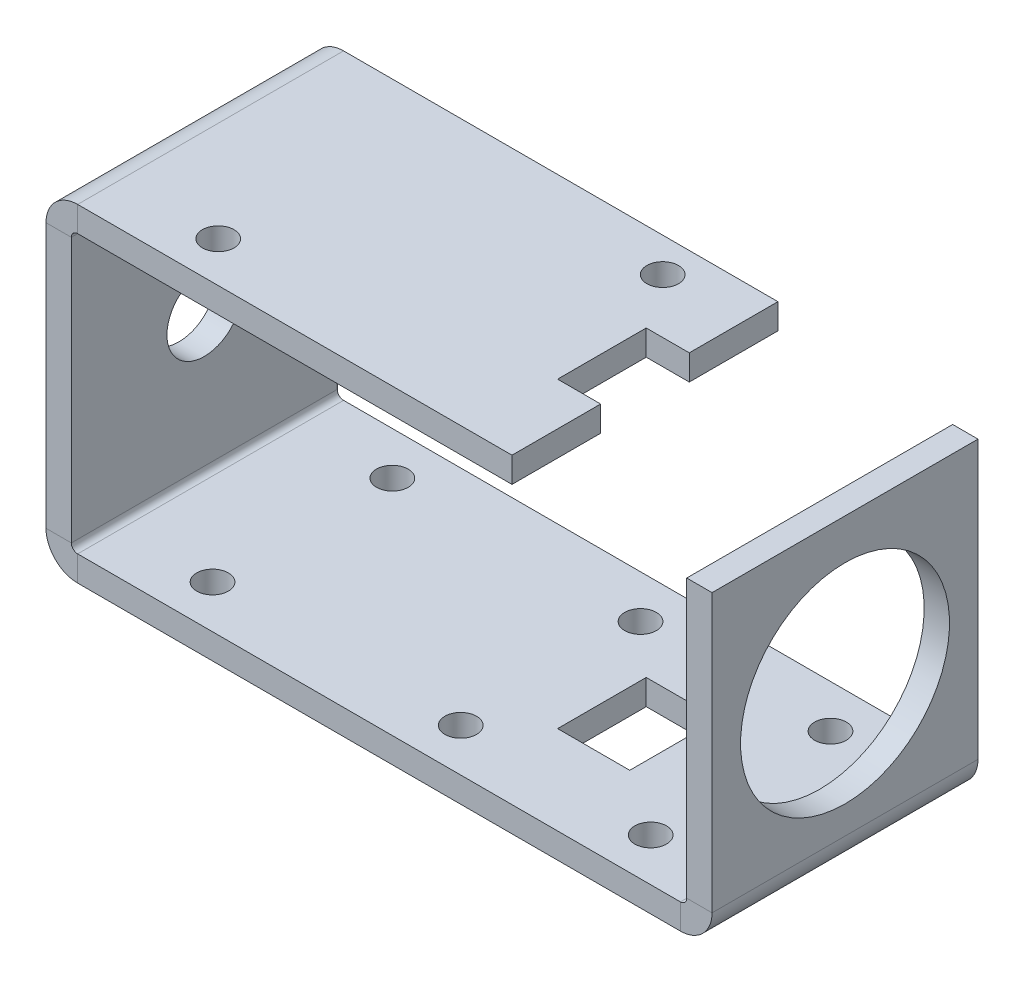
SolidWorks part; units mm, degrees
note: The reader was unsure of these and kept them because the rebuilt part matched: flange length of "Edge-Flange1", "Edge-Flange2", "Edge-Flange3".
ref_plane "Front Plane" through (0, 0, 0) normal (0, 0, 1) x (1, 0, 0)
ref_plane "Top Plane" through (0, 0, 0) normal (0, 1, 0) x (1, 0, 0)
ref_plane "Right Plane" through (0, 0, 0) normal (1, 0, 0) x (0, 0, -1)
sketch "Sketch1" plane through (0, 0, 0) normal (0, 1, 0) x (1, 0, 0)
  line L1 (-26.3, -10.5) -> (26.3, -10.5)
  line L2 (-26.3, -10.5) -> (-26.3, 10.5)
  line L3 (-26.3, 10.5) -> (26.3, 10.5)
  line L4 (26.3, -10.5) -> (26.3, 10.5)
  line L5 (-26.3, -10.5) -> (26.3, 10.5) construction
  line L6 (-26.3, 10.5) -> (26.3, -10.5) construction
  point P0 (0, 0)
  dimension "D1" = 21
  dimension "D2" = 52.6
base flange "Base-Flange1" sketch "Sketch1" thickness 2 reverse thickness direction no parameters "D1"=1
edge flange "Edge-Flange1" sketch "Sketch8" flange angle 90 flange length 25.9 flange position material inside bend radius 0.5 thickness 2 relief rectangular parameters "D6"=10
sketch "Sketch8" plane through (-26.3, 0, 0) normal (-1, 0, 0) x (0, 0, 1)
  line L0 (-10.5, 0) -> (10.5, 0) construction
  line L1 (-10.5, 0) -> (10.5, 0)
  line L2 (-10.5, 0) -> (-10.5, 23.9)
  line L3 (-10.5, 23.9) -> (10.5, 23.9)
  line L4 (10.5, 23.9) -> (10.5, 0)
bend "EdgeBend1" bend radius 0.5 bend angle 90 parameters "D5"=1
edge flange "Edge-Flange2" sketch "Sketch11" flange angle 90 flange length 36.8 flange position material inside bend radius 0.5 thickness 2 relief rectangular parameters "D6"=10
sketch "Sketch11" plane through (-24.3, 23.9, 0) normal (0, 1, 0) x (0, 0, 1)
  line L0 (10.5, 0) -> (-10.5, 0) construction
  line L1 (10.5, 0) -> (-10.5, 0)
  line L2 (-10.5, 0) -> (-10.5, 34.8)
  line L3 (-10.5, 34.8) -> (10.5, 34.8)
  line L4 (10.5, 34.8) -> (10.5, 0)
bend "EdgeBend2" bend radius 0.5 bend angle 90 parameters "D5"=2
edge flange "Edge-Flange3" sketch "Sketch14" flange angle 90 flange length 23.6 flange position material inside bend radius 0.5 thickness 2 relief rectangular parameters "D6"=10
sketch "Sketch14" plane through (26.3, 0, 0) normal (1, 0, 0) x (0, 0, -1)
  line L0 (-10.5, 0) -> (10.5, 0) construction
  line L1 (-10.5, 0) -> (10.5, 0)
  line L2 (-10.5, 0) -> (-10.5, 21.6)
  line L3 (-10.5, 21.6) -> (10.5, 21.6)
  line L4 (10.5, 21.6) -> (10.5, 0)
bend "EdgeBend3" bend radius 0.5 bend angle 90 parameters "D5"=3
sketch "Sketch15" plane through (0, 23.9, 0) normal (0, 1, 0) x (1, 0, 0)
  line L0 (10.5, -10.5) -> (10.5, 10.5) construction
  line L1 (10.5, 3.5) -> (7.1, 3.5)
  line L2 (10.5, 3.5) -> (10.5, -3.5)
  line L3 (10.5, -3.5) -> (7.1, -3.5)
  line L4 (7.1, 3.5) -> (7.1, -3.5)
  point P6 (7.1, 0)
  dimension "D1" = 7
  dimension "D2" = 3.4
extrude "Cut-Extrude1" cut sketch "Sketch15" against normal blind 10
sketch "Sketch16" plane through (0, 23.9, 0) normal (0, 1, 0) x (1, 0, 0)
  line L0 (-26.3, -10.5) -> (-26.3, 10.5) construction
  line L1 (-23.8, -10.5) -> (10.5, -10.5) construction
  line L2 (10.5, 10.5) -> (-23.8, 10.5) construction
  circle A0 centre (4.1, 7.8) radius 1.25
  circle A1 centre (-15.9, -7.3) radius 1.25
  dimension "D1" = 2.5
  dimension "D2" = 2.5
  dimension "D3" = 10.4
  dimension "D4" = 3.2
  dimension "D5" = 2.7
  dimension "D6" = 30.4
extrude "Cut-Extrude2" cut sketch "Sketch16" against normal blind 2
sketch "Sketch18" plane through (0, 23.9, 0) normal (0, 1, 0) x (1, 0, 0)
  line L0 (7.1, -3.5) -> (10.5, -3.5) construction
  line L1 (7.1, 3.5) -> (12.8, 3.5)
  line L2 (7.1, 3.5) -> (7.1, -3.5)
  line L3 (7.1, -3.5) -> (12.8, -3.5)
  line L4 (12.8, 3.5) -> (12.8, -3.5)
  dimension "D1" = 5.7
extrude "Cut-Extrude3" cut sketch "Sketch18" against normal through all
sketch "Sketch19" plane through (-26.3, 0, 0) normal (-1, 0, 0) x (0, 0, 1)
  line L0 (-10.5, 21.4) -> (-10.5, 0.5) construction
  circle A0 centre (0, 10.95) radius 2.95
  point P4 (-10.5, 10.95)
  dimension "D1" = 5.9
extrude "Cut-Extrude4" cut sketch "Sketch19" against normal blind 2
sketch "Sketch20" plane through (0, -2, 0) normal (0, -1, 0) x (1, 0, 0)
  line L0 (23.8, -10.5) -> (-23.8, -10.5) construction
  line L1 (-23.8, 10.5) -> (23.8, 10.5) construction
  line L2 (-26.3, 10.5) -> (-26.3, -10.5) construction
  line L3 (26.3, -10.5) -> (26.3, 10.5) construction
  circle A0 centre (-16.55, 7.1) radius 1.25
  circle A1 centre (3.05, 7.1) radius 1.25
  circle A2 centre (18.05, 7.1) radius 1.25
  circle A3 centre (-16.55, -7.1) radius 1.25
  circle A4 centre (3.05, -7.1) radius 1.25
  circle A5 centre (18.05, -7.1) radius 1.25
  point P14 (19.3, 7.1)
  point P21 (-17.8, 7.1)
  point P22 (4.3, 7.1)
  dimension "D1" = 2.5
  dimension "D2" = 3.4
  dimension "D3" = 3.4
  dimension "D4" = 8.5
  dimension "D5" = 7
  dimension "D6" = 22
extrude "Cut-Extrude5" cut sketch "Sketch20" against normal blind 2
sketch "Sketch21" plane through (26.3, 0, 0) normal (1, 0, 0) x (0, 0, -1)
  line L0 (10.5, 21.6) -> (-10.5, 21.6) construction
  circle A0 centre (0, 10.95) radius 8.25
  dimension "D1" = 16.5
  dimension "D2" = 10.65
extrude "Cut-Extrude6" cut sketch "Sketch21" against normal blind 2
other "Move Face1" face at (25.3, 21.6, 0) parameters "D1"=0.8
sketch "Bend-Lines1" [suppressed] plane through (0, 0, 0) normal (0, 1, 0) x (1, 0, 0)
sketch "Bounding-Box1" [suppressed] plane through (0, 0, 0) normal (0, 1, 0) x (1, 0, 0)
sheet metal parameters "Sheet-Metal1" thickness 2 parameters "D1"=1
flat pattern "Flat-Pattern1" [suppressed]
sketch "Bend-Lines2" plane through (0, 0, 0) normal (0, 1, 0) x (1, 0, 0)
sketch3d "Bounding-Box2" [suppressed]
  line L0 (-26.55, 10.5, 0) -> (26.55, 10.5, 0) construction
  line L1 (-26.55, -10.5, 0) -> (26.55, -10.5, 0) construction
  line L2 (-26.55, 10.5, 0) -> (-26.55, -10.5, 0) construction
  line L3 (26.55, 10.5, 0) -> (26.55, -10.5, 0) construction
sheet metal parameters "Sheet-Metal2" thickness 2 parameters "D1"=1
flat pattern "Flat-Pattern1"
sketch "Bend-Lines2" plane through (0, 0, 0) normal (0, 1, 0) x (1, 0, 0)
  line L0 (-25.1208, 10.5) -> (-25.1208, -10.5) construction
  line L1 (-25.1208, 10.5) -> (-25.1208, -10.5) construction
sketch3d "Bounding-Box2" [suppressed]
  line L0 (26.55, 10.5, 0) -> (-49.5916, 10.5, 0) construction
  line L1 (26.55, -10.5, 0) -> (-49.5916, -10.5, 0) construction
  line L2 (26.55, 10.5, 0) -> (26.55, -10.5, 0) construction
  line L3 (-49.5916, 10.5, 0) -> (-49.5916, -10.5, 0) construction
bend of the flat pattern "Flatten-<EdgeBend1>1"
sheet metal parameters "Sheet-Metal3" thickness 2 parameters "D1"=1
flat pattern "Flat-Pattern1"
sketch "Bend-Lines2" plane through (0, 0, 0) normal (0, 1, 0) x (1, 0, 0)
  line L0 (-25.1208, 10.5) -> (-25.1208, -10.5) construction
  line L1 (-25.1208, 10.5) -> (-25.1208, -10.5) construction
  line L2 (-48.1624, 10.5) -> (-48.1624, -10.5) construction
  line L3 (-48.1624, 10.5) -> (-48.1624, -10.5) construction
sketch3d "Bounding-Box2" [suppressed]
  line L0 (26.55, 10.5, 0) -> (-83.5332, 10.5, 0) construction
  line L1 (26.55, -10.5, 0) -> (-83.5332, -10.5, 0) construction
  line L2 (26.55, 10.5, 0) -> (26.55, -10.5, 0) construction
  line L3 (-83.5332, 10.5, 0) -> (-83.5332, -10.5, 0) construction
bend of the flat pattern "Flatten-<EdgeBend1>1"
bend of the flat pattern "Flatten-<EdgeBend2>1"
sheet metal parameters "Sheet-Metal4" thickness 2 parameters "D1"=1
flat pattern "Flat-Pattern1"
sketch "Bend-Lines2" plane through (0, 0, 0) normal (0, 1, 0) x (1, 0, 0)
  line L0 (-25.1208, 10.5) -> (-25.1208, -10.5) construction
  line L1 (-25.1208, 10.5) -> (-25.1208, -10.5) construction
  line L2 (-48.1624, 10.5) -> (-48.1624, -10.5) construction
  line L3 (-48.1624, 10.5) -> (-48.1624, -10.5) construction
  line L4 (25.1208, -10.5) -> (25.1208, 10.5) construction
  line L5 (25.1208, -10.5) -> (25.1208, 10.5) construction
sketch3d "Bounding-Box2" [suppressed]
  line L0 (48.2916, 10.5, 0) -> (-83.5332, 10.5, 0) construction
  line L1 (48.2916, -10.5, 0) -> (-83.5332, -10.5, 0) construction
  line L2 (48.2916, 10.5, 0) -> (48.2916, -10.5, 0) construction
  line L3 (-83.5332, 10.5, 0) -> (-83.5332, -10.5, 0) construction
bend of the flat pattern "Flatten-<EdgeBend1>1"
bend of the flat pattern "Flatten-<EdgeBend2>1"
bend of the flat pattern "Flatten-<EdgeBend3>1"
sheet metal parameters "Sheet-Metal5" thickness 2 parameters "D1"=1
flat pattern "Flat-Pattern1" [suppressed]
sketch "Bend-Lines2" plane through (0, 0, 0) normal (0, 1, 0) x (1, 0, 0)
  line L0 (-25.2281, 10.5) -> (-25.2281, -10.5) construction
  line L1 (-25.2281, 10.5) -> (-25.2281, -10.5) construction
  line L2 (-48.4843, 10.5) -> (-48.4843, -10.5) construction
  line L3 (-48.4843, 10.5) -> (-48.4843, -10.5) construction
  line L4 (25.2281, -10.5) -> (25.2281, 10.5) construction
  line L5 (25.2281, -10.5) -> (25.2281, 10.5) construction
sketch3d "Bounding-Box2" [suppressed]
  line L0 (48.5062, 10.5, 0) -> (-83.9624, 10.5, 0) construction
  line L1 (48.5062, -10.5, 0) -> (-83.9624, -10.5, 0) construction
  line L2 (48.5062, 10.5, 0) -> (48.5062, -10.5, 0) construction
  line L3 (-83.9624, 10.5, 0) -> (-83.9624, -10.5, 0) construction
bend of the flat pattern "Flatten-<EdgeBend1>1"
bend of the flat pattern "Flatten-<EdgeBend2>1"
bend of the flat pattern "Flatten-<EdgeBend3>1"
sketch "Sketch16-1" [suppressed] plane through (-73.7124, -2, 0) normal (0, -1, 0) x (-1, 0, 0)
  line L0 (-26.55, -10.5) -> (-26.55, 10.5) construction
  line L1 (-122.2186, -10.5) -> (10.25, -10.5) construction
  line L2 (10.25, 10.5) -> (-122.2186, 10.5) construction
  circle A0 centre (3.85, 7.8) radius 1.25
  circle A1 centre (-16.15, -7.3) radius 1.25
  dimension "D1" = 2.5
  dimension "D2" = 2.5
  dimension "D3" = 10.4
  dimension "D4" = 3.2
  dimension "D5" = 2.7
  dimension "D6" = 30.4
sheet metal parameters "Sheet-Metal6" thickness 2 parameters "D1"=1
flat pattern "Flat-Pattern1" [suppressed]
sketch "Bend-Lines2" plane through (0, 0, 0) normal (0, 1, 0) x (1, 0, 0)
  line L0 (-25.2281, 10.5) -> (-25.2281, -10.5) construction
  line L1 (-25.2281, 10.5) -> (-25.2281, -10.5) construction
  line L2 (-48.4843, 10.5) -> (-48.4843, -10.5) construction
  line L3 (-48.4843, 10.5) -> (-48.4843, -10.5) construction
  line L4 (25.2281, -10.5) -> (25.2281, 10.5) construction
  line L5 (25.2281, -10.5) -> (25.2281, 10.5) construction
sketch3d "Bounding-Box2" [suppressed]
  line L0 (48.5062, 10.5, 0) -> (-83.9624, 10.5, 0) construction
  line L1 (48.5062, -10.5, 0) -> (-83.9624, -10.5, 0) construction
  line L2 (48.5062, 10.5, 0) -> (48.5062, -10.5, 0) construction
  line L3 (-83.9624, 10.5, 0) -> (-83.9624, -10.5, 0) construction
bend of the flat pattern "Flatten-<EdgeBend1>1"
bend of the flat pattern "Flatten-<EdgeBend2>1"
bend of the flat pattern "Flatten-<EdgeBend3>1"
sketch "Sketch16-1" [suppressed] plane through (-73.7124, -2, 0) normal (0, -1, 0) x (-1, 0, 0)
  line L0 (-26.55, -10.5) -> (-26.55, 10.5) construction
  line L1 (-122.2186, -10.5) -> (10.25, -10.5) construction
  line L2 (10.25, 10.5) -> (-122.2186, 10.5) construction
  circle A0 centre (3.85, 7.8) radius 1.25
  circle A1 centre (-16.15, -7.3) radius 1.25
  dimension "D1" = 2.5
  dimension "D2" = 2.5
  dimension "D3" = 10.4
  dimension "D4" = 3.2
  dimension "D5" = 2.7
  dimension "D6" = 30.4
sheet metal parameters "Sheet-Metal7" thickness 2 parameters "D1"=1
flat pattern "Flat-Pattern1" [suppressed]
sketch "Bend-Lines2" plane through (0, 0, 0) normal (0, 1, 0) x (1, 0, 0)
  line L0 (-25.2281, 10.5) -> (-25.2281, -10.5) construction
  line L1 (-25.2281, 10.5) -> (-25.2281, -10.5) construction
  line L2 (-48.4843, 10.5) -> (-48.4843, -10.5) construction
  line L3 (-48.4843, 10.5) -> (-48.4843, -10.5) construction
  line L4 (25.2281, -10.5) -> (25.2281, 10.5) construction
  line L5 (25.2281, -10.5) -> (25.2281, 10.5) construction
sketch3d "Bounding-Box2" [suppressed]
  line L0 (48.5062, 10.5, 0) -> (-83.9624, 10.5, 0) construction
  line L1 (48.5062, -10.5, 0) -> (-83.9624, -10.5, 0) construction
  line L2 (48.5062, 10.5, 0) -> (48.5062, -10.5, 0) construction
  line L3 (-83.9624, 10.5, 0) -> (-83.9624, -10.5, 0) construction
bend of the flat pattern "Flatten-<EdgeBend1>1"
bend of the flat pattern "Flatten-<EdgeBend2>1"
bend of the flat pattern "Flatten-<EdgeBend3>1"
sketch "Sketch16-1" plane through (-73.7124, -2, 0) normal (0, -1, 0) x (-1, 0, 0)
  line L0 (-26.55, -10.5) -> (-26.55, 10.5) construction
  line L1 (-122.2186, -10.5) -> (10.25, -10.5) construction
  line L2 (10.25, 10.5) -> (-122.2186, 10.5) construction
  circle A0 centre (3.85, 7.8) radius 1.25
  circle A1 centre (-16.15, -7.3) radius 1.25
  dimension "D1" = 2.5
  dimension "D2" = 2.5
  dimension "D3" = 10.4
  dimension "D4" = 3.2
  dimension "D5" = 2.7
  dimension "D6" = 30.4
sheet metal parameters "Sheet-Metal8" thickness 2 parameters "D1"=1
flat pattern "Flat-Pattern1" [suppressed]
sketch "Bend-Lines2" plane through (0, 0, 0) normal (0, 1, 0) x (1, 0, 0)
  line L0 (-25.2281, 10.5) -> (-25.2281, -10.5) construction
  line L1 (-25.2281, 10.5) -> (-25.2281, -10.5) construction
  line L2 (-48.4843, 10.5) -> (-48.4843, -10.5) construction
  line L3 (-48.4843, 10.5) -> (-48.4843, -10.5) construction
  line L4 (25.2281, -10.5) -> (25.2281, 10.5) construction
  line L5 (25.2281, -10.5) -> (25.2281, 10.5) construction
sketch3d "Bounding-Box2" [suppressed]
  line L0 (48.5062, 10.5, 0) -> (-83.9624, 10.5, 0) construction
  line L1 (48.5062, -10.5, 0) -> (-83.9624, -10.5, 0) construction
  line L2 (48.5062, 10.5, 0) -> (48.5062, -10.5, 0) construction
  line L3 (-83.9624, 10.5, 0) -> (-83.9624, -10.5, 0) construction
bend of the flat pattern "Flatten-<EdgeBend1>1"
bend of the flat pattern "Flatten-<EdgeBend2>1"
bend of the flat pattern "Flatten-<EdgeBend3>1"
sketch "Sketch16-1" plane through (-73.7124, -2, 0) normal (0, -1, 0) x (-1, 0, 0)
  line L0 (-26.55, -10.5) -> (-26.55, 10.5) construction
  line L1 (-122.2186, -10.5) -> (10.25, -10.5) construction
  line L2 (10.25, 10.5) -> (-122.2186, 10.5) construction
  circle A0 centre (3.85, 7.8) radius 1.25
  circle A1 centre (-16.15, -7.3) radius 1.25
  dimension "D1" = 2.5
  dimension "D2" = 2.5
  dimension "D3" = 10.4
  dimension "D4" = 3.2
  dimension "D5" = 2.7
  dimension "D6" = 30.4
sheet metal parameters "Sheet-Metal9" thickness 2 parameters "D1"=1
flat pattern "Flat-Pattern1" [suppressed]
sketch "Bend-Lines2" plane through (0, 0, 0) normal (0, 1, 0) x (1, 0, 0)
  line L0 (-25.2281, 10.5) -> (-25.2281, -10.5) construction
  line L1 (-25.2281, 10.5) -> (-25.2281, -10.5) construction
  line L2 (-48.4843, 10.5) -> (-48.4843, -10.5) construction
  line L3 (-48.4843, 10.5) -> (-48.4843, -10.5) construction
  line L4 (25.2281, -10.5) -> (25.2281, 10.5) construction
  line L5 (25.2281, -10.5) -> (25.2281, 10.5) construction
sketch3d "Bounding-Box2" [suppressed]
  line L0 (48.5062, 10.5, 0) -> (-83.9624, 10.5, 0) construction
  line L1 (48.5062, -10.5, 0) -> (-83.9624, -10.5, 0) construction
  line L2 (48.5062, 10.5, 0) -> (48.5062, -10.5, 0) construction
  line L3 (-83.9624, 10.5, 0) -> (-83.9624, -10.5, 0) construction
bend of the flat pattern "Flatten-<EdgeBend1>1"
bend of the flat pattern "Flatten-<EdgeBend2>1"
bend of the flat pattern "Flatten-<EdgeBend3>1"
sketch "Sketch16-1" plane through (-73.7124, -2, 0) normal (0, -1, 0) x (-1, 0, 0)
  line L0 (-26.55, -10.5) -> (-26.55, 10.5) construction
  line L1 (-122.2186, -10.5) -> (10.25, -10.5) construction
  line L2 (10.25, 10.5) -> (-122.2186, 10.5) construction
  circle A0 centre (3.85, 7.8) radius 1.25
  circle A1 centre (-16.15, -7.3) radius 1.25
  dimension "D1" = 2.5
  dimension "D2" = 2.5
  dimension "D3" = 10.4
  dimension "D4" = 3.2
  dimension "D5" = 2.7
  dimension "D6" = 30.4
sheet metal parameters "Sheet-Metal10" thickness 2 parameters "D1"=1
flat pattern "Flat-Pattern1" [suppressed]
sketch "Bend-Lines2" plane through (0, 0, 0) normal (0, 1, 0) x (1, 0, 0)
  line L0 (-25.2281, 10.5) -> (-25.2281, -10.5) construction
  line L1 (-25.2281, 10.5) -> (-25.2281, -10.5) construction
  line L2 (-48.4843, 10.5) -> (-48.4843, -10.5) construction
  line L3 (-48.4843, 10.5) -> (-48.4843, -10.5) construction
  line L4 (25.2281, -10.5) -> (25.2281, 10.5) construction
  line L5 (25.2281, -10.5) -> (25.2281, 10.5) construction
sketch3d "Bounding-Box2" [suppressed]
  line L0 (47.5062, 10.5, 0) -> (-83.9624, 10.5, 0) construction
  line L1 (47.5062, -10.5, 0) -> (-83.9624, -10.5, 0) construction
  line L2 (47.5062, 10.5, 0) -> (47.5062, -10.5, 0) construction
  line L3 (-83.9624, 10.5, 0) -> (-83.9624, -10.5, 0) construction
bend of the flat pattern "Flatten-<EdgeBend1>1"
bend of the flat pattern "Flatten-<EdgeBend2>1"
bend of the flat pattern "Flatten-<EdgeBend3>1"
sketch "Sketch16-1" plane through (-73.7124, -2, 0) normal (0, -1, 0) x (-1, 0, 0)
  line L0 (-26.55, -10.5) -> (-26.55, 10.5) construction
  line L1 (-121.2186, -10.5) -> (10.25, -10.5) construction
  line L2 (10.25, 10.5) -> (-121.2186, 10.5) construction
  circle A0 centre (3.85, 7.8) radius 1.25
  circle A1 centre (-16.15, -7.3) radius 1.25
  dimension "D1" = 2.5
  dimension "D2" = 2.5
  dimension "D3" = 10.4
  dimension "D4" = 3.2
  dimension "D5" = 2.7
  dimension "D6" = 30.4
sheet metal parameters "Sheet-Metal11" thickness 2 parameters "D1"=1
flat pattern "Flat-Pattern1"
sketch "Bend-Lines2" plane through (0, 0, 0) normal (0, 1, 0) x (1, 0, 0)
  line L0 (24.9781, -10.5) -> (24.9781, 10.5) construction
  line L1 (-48.2343, 10.5) -> (-48.2343, -10.5) construction
  line L2 (-24.9781, 10.5) -> (-24.9781, -10.5) construction
  line L3 (24.9781, -10.5) -> (24.9781, 10.5) construction
  line L4 (-48.2343, 10.5) -> (-48.2343, -10.5) construction
  line L5 (-24.9781, 10.5) -> (-24.9781, -10.5) construction
sketch3d "Bounding-Box2" [suppressed]
  line L0 (48.0562, 10.5, 0) -> (-83.7124, 10.5, 0) construction
  line L1 (48.0562, -10.5, 0) -> (-83.7124, -10.5, 0) construction
  line L2 (48.0562, 10.5, 0) -> (48.0562, -10.5, 0) construction
  line L3 (-83.7124, 10.5, 0) -> (-83.7124, -10.5, 0) construction
bend of the flat pattern "Flatten-<EdgeBend3>2"
bend of the flat pattern "Flatten-<EdgeBend2>2"
bend of the flat pattern "Flatten-<EdgeBend1>2"
